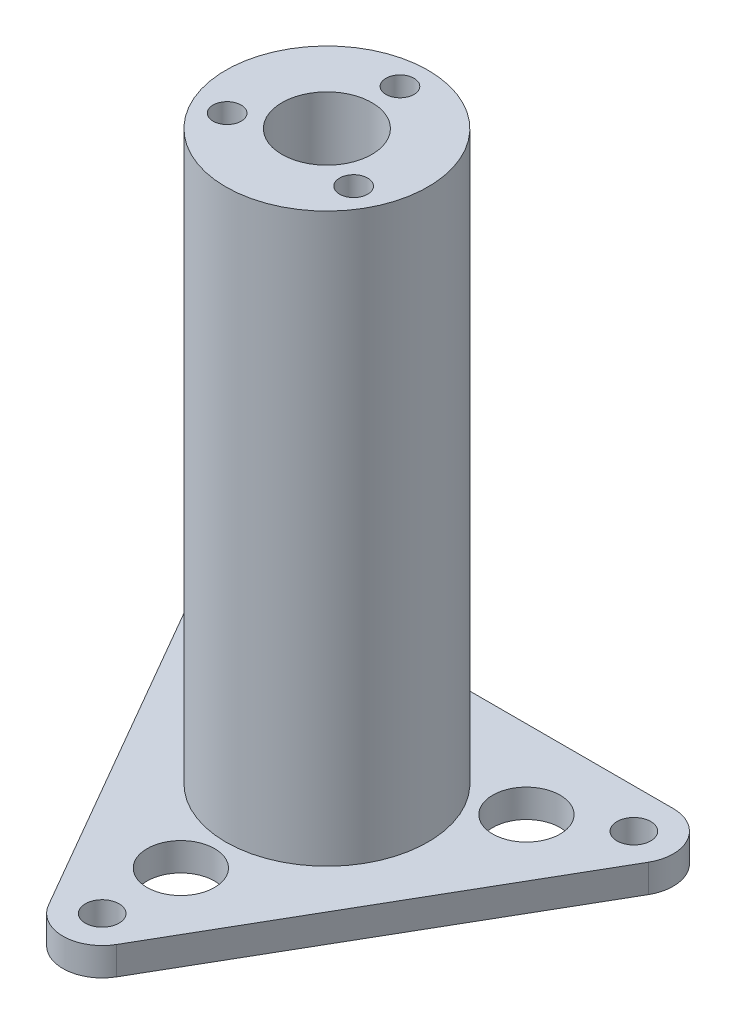
SolidWorks part; units mm, degrees
material "6061 合金"
ref_plane "前视基准面" through (0, 0, 0) normal (0, 0, 1) x (1, 0, 0)
ref_plane "上视基准面" through (0, 0, 0) normal (0, 1, 0) x (1, 0, 0)
ref_plane "右视基准面" through (0, 0, 0) normal (1, 0, 0) x (0, 0, -1)
sketch "草图2" plane through (0, 0, 0) normal (0, 0, 1) x (1, 0, 0)
  line L0 (0, 0) -> (0, 53) construction
  line L1 (0, 0) -> (23.5, 0)
  line L4 (9, 2.5) -> (9, 53)
  line L5 (9, 53) -> (0, 53)
  line L6 (0, 53) -> (0, 0)
  line L8 (23.5, 2.5) -> (23.5, 0)
  line L12 (23.5, 2.5) -> (9, 2.5)
  dimension "D1" = 9
  dimension "D2" = 2.5
  dimension "D3" = 53
  dimension "D5" = 23.5
revolve "旋转1" add sketch "草图2" angle 360 about L0
sketch "草图9" plane through (0, 0, 0) normal (0, -1, 0) x (1, 0, 0)
  line L0 (0, 0) -> (0, 20) construction
  line L1 (-3.0311, 21.75) -> (-20.3516, -8.25)
  line L2 (20.3516, -8.25) -> (3.0311, 21.75)
  line L3 (-17.3205, -13.5) -> (17.3205, -13.5)
  circle A0 centre (0, 20) radius 1.5
  circle A1 centre (17.3205, -10) radius 1.5
  circle A2 centre (-17.3205, -10) radius 1.5
  circle A3 centre (0, 0) radius 20 construction
  circle A4 centre (0, 0) radius 23.5 construction
  arc A5 (3.0311, 21.75) -> (-3.0311, 21.75) centre (0, 20) ccw
  arc A6 (17.3205, -13.5) -> (20.3516, -8.25) centre (17.3205, -10) ccw
  arc A7 (-20.3516, -8.25) -> (-17.3205, -13.5) centre (-17.3205, -10) ccw
  circle A8 centre (0, 0) radius 9 construction
  circle A9 centre (0, 13) radius 3
  circle A10 centre (11.2583, -6.5) radius 3
  circle A11 centre (-11.2583, -6.5) radius 3
  dimension "D2" = 3
  dimension "D4" = 18
  dimension "D1" = 40
  dimension "D5" = 6
  dimension "D6" = 13
  dimension "D3" = 3
extrude "切除-拉伸2" cut sketch "草图9" against normal through all flip side to cut
hole_wizard "M3 螺纹孔1" positions "草图13" profile "草图14" tap size "M3" standard "GB"
sketch "草图13" plane through (0, 53, 0) normal (0, 1, 0) x (1, 0, 0)
  circle A0 centre (0, 0) radius 6.5 construction
  circle A1 centre (0, 0) radius 9 construction
  point P9 (0, 6.5)
  point P15 (5.6292, -3.25)
  point P16 (-5.6292, -3.25)
  point P18 (-4.7338, -4.4543)
  point P19 (5.6527, -3.2089)
  dimension "D1" = 2.5
  dimension "D2" = 3
sketch "草图14" plane through (-5.6292, 53, 3.25) normal (1, 0, 0) x (0, 0, 1)
  line L0 (0, 0) -> (0, 8.2511)
  line L1 (0, 8.2511) -> (1.25, 7.5)
  line L2 (1.25, 7.5) -> (1.25, 0)
  line L5 (1.25, 0) -> (0, 0)
  line L10 (0, 8.2511) -> (-1.25, 7.5) construction
  line L11 (0, -6.35) -> (0, 107.95) construction
  dimension "螺纹孔钻头直径" = 2.5
  dimension "螺纹孔钻头深度" = 7.5
  dimension "导头角度" = 118
cosmetic thread "孔螺蚊线1" parameters "D1"=6, "D2"=3
cosmetic thread "孔螺蚊线2" parameters "D1"=6, "D2"=3
cosmetic thread "孔螺蚊线3" parameters "D1"=6, "D2"=3
sketch "草图10" plane through (0, 53, 0) normal (0, 1, 0) x (1, 0, 0)
  circle A0 centre (0, 0) radius 4
  circle A2 centre (0, 0) radius 9 construction
  dimension "D1" = 5
extrude "切除-拉伸3" cut sketch "草图10" against normal through all
sketch "草图15" plane through (0, 0, 0) normal (0, -1, 0) x (1, 0, 0)
  circle A0 centre (0, 0) radius 6
  dimension "D1" = 12
extrude "切除-拉伸4" cut sketch "草图15" against normal blind 40
chamfer "倒角1" distance 2 angle 45 1 edges at (0, 40, -6)
